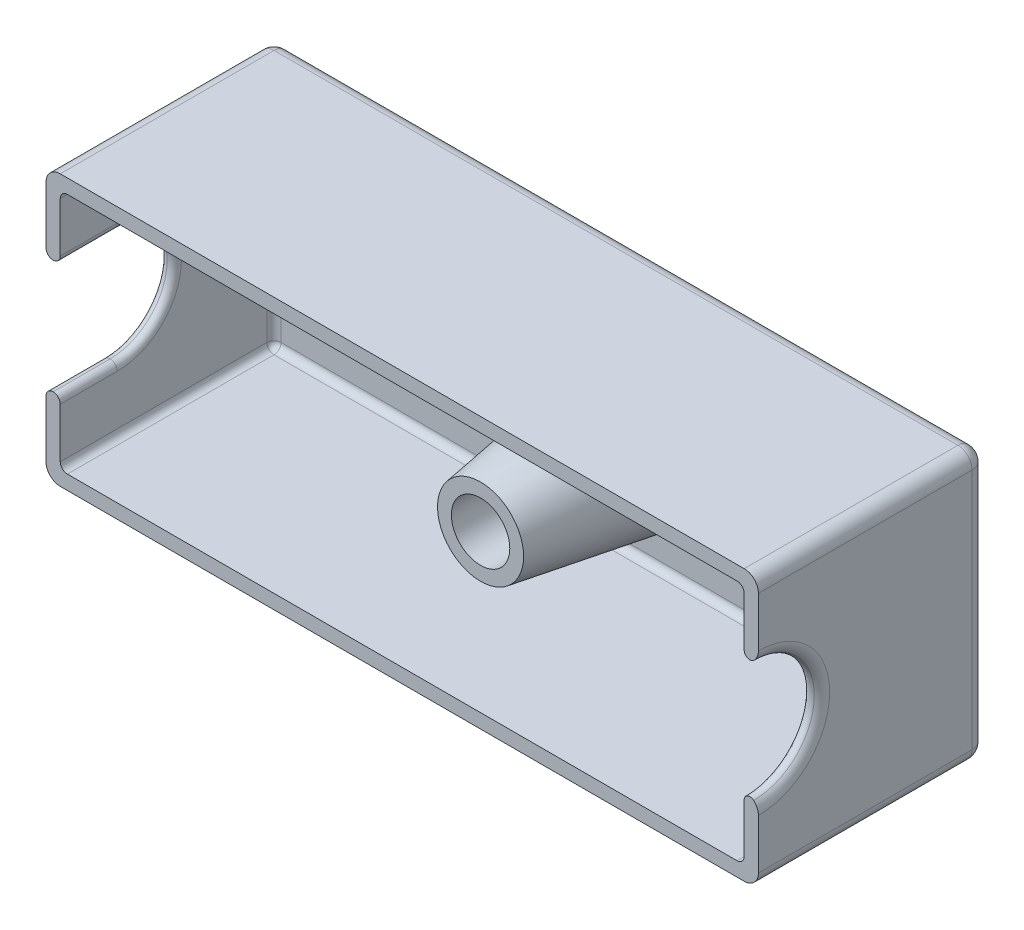
SolidWorks part; units mm, degrees
material "PVC 0.007 Plasticizado"
ref_plane "Plano frontal" through (0, 0, 0) normal (0, 0, 1) x (1, 0, 0)
ref_plane "Plano superior" through (0, 0, 0) normal (0, 1, 0) x (1, 0, 0)
ref_plane "Plano direito" through (0, 0, 0) normal (1, 0, 0) x (0, 0, -1)
sketch "Esboço1" plane through (0, 0, 0) normal (0, 0, 1) x (1, 0, 0)
  line L8 (-24, 8.5) -> (24, 8.5)
  line L9 (24, 8.5) -> (24, -8.5)
  line L10 (24, -8.5) -> (-24, -8.5)
  line L11 (-24, -8.5) -> (-24, 8.5)
  line L12 (-25, 9.5) -> (25, 9.5)
  line L13 (-25, 9.5) -> (-25, -9.5)
  line L14 (-25, -9.5) -> (25, -9.5)
  line L15 (25, -9.5) -> (25, 9.5)
  point P4 (0, 8.5)
  point P5 (24, 0)
  point P8 (0, 9.5)
  dimension "D1" = 48
  dimension "D2" = 17
  dimension "D3" = 1
  dimension "D4" = 1
  dimension "D5" = 1
extrude "Ressalto-extrusão1" add sketch "Esboço1" along normal blind 15
sketch "Esboço2" plane through (0, 0, 0) normal (0, 0, -1) x (-1, 0, 0)
  line L0 (-25, 9.5) -> (25, 9.5)
  line L1 (25, 9.5) -> (25, -9.5)
  line L2 (25, -9.5) -> (-25, -9.5)
  line L3 (-25, -9.5) -> (-25, 9.5)
extrude "Ressalto-extrusão2" add sketch "Esboço2" along normal blind 1
sketch "Esboço3" plane through (0, 0, 0) normal (0, 0, 1) x (1, 0, 0)
  line L0 (-24, 8.5) -> (-24, -8.5) construction
  line L1 (24, 8.5) -> (-24, 8.5) construction
  circle A1 centre (3, 0) radius 3
  dimension "D1" = 27
  dimension "D4" = 6
  dimension "D2" = 8.5
extrude "Ressalto-extrusão3" add sketch "Esboço3" along normal blind 12.5
chamfer "Chanfro1" distance 2 angle 81 1 edges at (6, 0, 0) first distance on face at (6, 0, 0)
sketch "Esboço4" plane through (0, 0, -1) normal (0, 0, 1) x (1, 0, 0)
  circle A0 centre (3, 0) radius 4
  circle A1 centre (3, 0) radius 3.0202 construction
  dimension "D1" = 8
extrude "Corte-extrusão1" cut sketch "Esboço4" along normal blind 4
fillet "Filete2" radius 1 8 edges at (-25, -9.5, 7) (-25, 0, -1) (-25, 9.5, 7) (0, -9.5, -1) (25, -9.5, 7) (25, 0, -1) (0, 9.5, -1) (25, 9.5, 7)
sketch "Esboço5" plane through (-25, 0, 0) normal (-1, 0, 0) x (0, 0, 1)
  line L0 (15, 4) -> (11, 4)
  line L1 (15, 8.5) -> (15, -8.5) construction
  line L3 (11, -4) -> (15, -4)
  arc A2 (11, 4) -> (11, -4) centre (11, 0) ccw
  point P4 (0, 0)
  point P5 (0, 0)
  point P7 (0, 0)
  point P8 (0, 0)
  point P9 (0, 0)
  point P10 (0, 0)
  point P11 (0, 0)
  point P12 (0, 0)
  point P13 (7, 0)
  dimension "D1" = 8
  dimension "D2" = 4
extrude "Corte-extrusão2" cut sketch "Esboço5" against normal blind 3 and the other way through all
sketch "Esboço6" plane through (25, 0, 0) normal (1, 0, 0) x (0, 0, -1)
  line L0 (-15, -8.5) -> (-15, 8.5) construction
  line L1 (-15, 4) -> (-15, -4)
  arc A0 (-15, -4) -> (-15, 4) centre (-15, 0) ccw
  dimension "D1" = 4
extrude "Corte-extrusão3" cut sketch "Esboço6" against normal blind 3
fillet "Filete4" radius 1 1 edges at (25, 0, 11)
sketch "Esboço7" plane through (0, 0, 12.5) normal (0, 0, 1) x (1, 0, 0)
  circle A0 centre (3, 0) radius 2.05
  dimension "D1" = 4.1
extrude "Corte-extrusão4" cut sketch "Esboço7" against normal blind 15
fillet "Filete5" radius 1 1 edges at (7, 0, -1)
sketch "Esboço8" plane through (0, 0, -1) normal (0, 0, -1) x (-1, 0, 0)
  circle A0 centre (3.12, 5.39) radius 1.75
  point P2 (-3, 0)
  dimension "D1" = 6.12
  dimension "D3" = 3.5
  dimension "D2" = 5.39
extrude "Corte-extrusão5" cut sketch "Esboço8" against normal blind 3 contours A0
fillet "Filete6" radius 0.5 2 edges at (-1.37, 5.39, 0) (-4.87, 5.39, -1)
fillet "Filete10" radius 0.5 3 edges at (24, 0, 0) (0, -8.5, 0) (-24, 0, 0)
fillet "Filete11" radius 0.5 9 edges at (-23.8536, -8.3536, 0.1464) (-24, 8.5, 7.75) (-23.8536, 8.5, 0.1464) (0, 8.5, 0) (23.8536, 8.5, 0.1464) (23.8536, -8.3536, 0.1464) (-24, -8.5, 7.75) (24, 8.5, 7.75) (24, -8.5, 7.75)
fillet "Filete14" radius 0.4 1 edges at (24, 0, 11)
fillet "Filete17" radius 0.5 6 edges at (-24, 4, 13) (-24, -4, 13) (-25, -4, 13) (-25, 4, 13) (-24, 0, 7) (-25, 0, 7)
